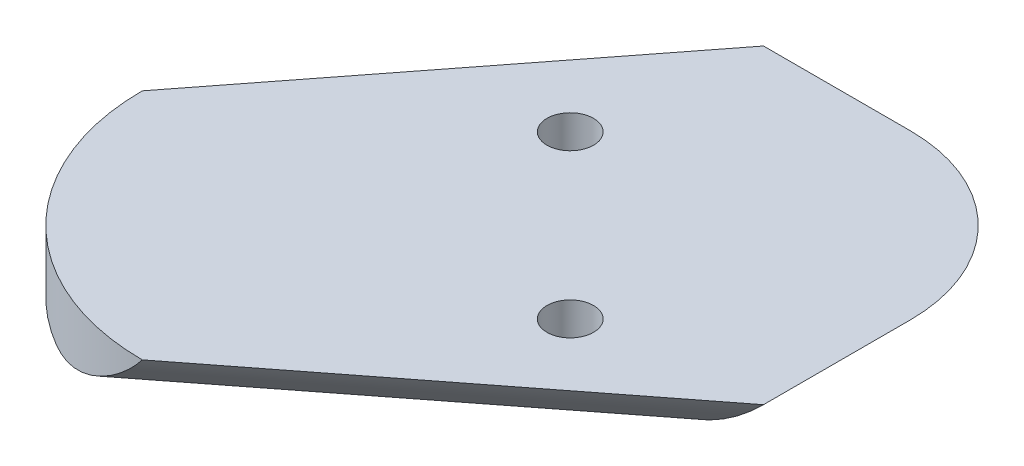
SolidWorks part; units mm, degrees
ref_plane "Front Plane" through (0, 0, 0) normal (0, 0, 1) x (1, 0, 0)
ref_plane "Top Plane" through (0, 0, 0) normal (0, 1, 0) x (1, 0, 0)
ref_plane "Right Plane" through (0, 0, 0) normal (1, 0, 0) x (0, 0, -1)
sketch "Sketch1" plane through (0, 0, 0) normal (0, 1, 0) x (1, 0, 0)
  line L0 (-20, 20) -> (-55, -25)
  line L1 (-20, 20) -> (-1.082, 20)
  line L2 (-20, 20) -> (-20, -20) construction
  line L3 (-20, -20) -> (20, -20) construction
  line L4 (20, -1.082) -> (20, -20)
  line L5 (-20, 20) -> (20, -20) construction
  line L6 (-20, -20) -> (20, 20) construction
  line L9 (-25, -55) -> (20, -20)
  line L10 (-55, -25) -> (-25, -25) construction
  line L11 (-25, -25) -> (-25, -55) construction
  arc A0 (-1.082, 20) -> (20, -1.082) centre (-1.082, -1.082) cw
  arc A1 (-55, -25) -> (-25, -55) centre (-25, -25) ccw
  point P0 (0, 0)
  dimension "D3" = 21.082
  dimension "D1" = 30
  dimension "D2" = 40
  dimension "D4" = 35
  dimension "D5" = 35
extrude "Boss-Extrude1" add sketch "Sketch1" along normal blind 8
fillet "Fillet1" radius 27.432 2 edges at (-10.541, 0, -20) (20, 0, 10.541)
fillet "Fillet3" radius 14 4 edges at (-45.0299, 0, 12.1813) (-12.1813, 0, 45.0299) (-26.9125, 2.0788, -11.1125) (11.1125, 2.0788, 26.9125)
sketch "Sketch2" plane through (0, 8, 0) normal (0, 1, 0) x (1, 0, 0)
  line L0 (-1.082, 20) -> (-20, 20) construction
  line L1 (20, -20) -> (20, -1.082) construction
  circle A0 centre (-22.88, -2.01) radius 3
  circle A1 centre (-2.01, -22.88) radius 3
  dimension "D1" = 6
  dimension "D2" = 22.01
  dimension "D3" = 42.88
  dimension "D5" = 42.88
  dimension "22.01" = 22.01
extrude "Cut-Extrude1" cut sketch "Sketch2" against normal blind 6
